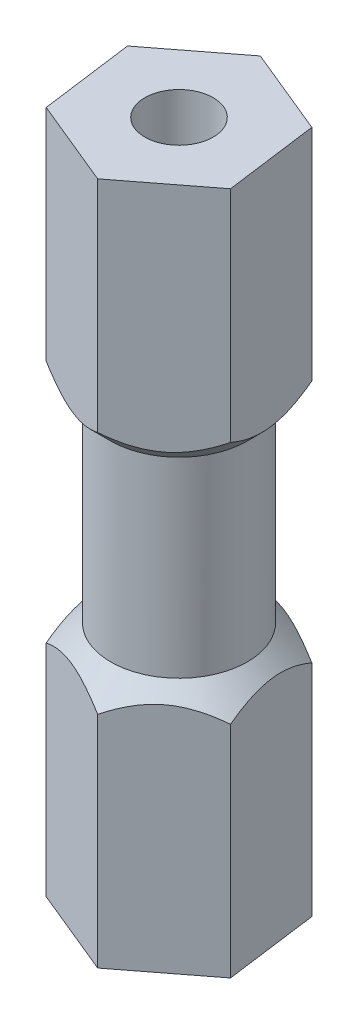
SolidWorks part; units mm, degrees
material "7050-T73510"
ref_plane "前视基准面" through (0, 0, 0) normal (0, 0, 1) x (1, 0, 0)
ref_plane "上视基准面" through (0, 0, 0) normal (0, 1, 0) x (1, 0, 0)
ref_plane "右视基准面" through (0, 0, 0) normal (1, 0, 0) x (0, 0, -1)
sketch "草图1" plane through (0, 0, 0) normal (0, 1, 0) x (1, 0, 0)
  circle A0 centre (0, 0) radius 2.5
  dimension "D1" = 5
extrude "凸台-拉伸1" add sketch "草图1" along normal blind 25
sketch "草图2" plane through (0, 25, 0) normal (0, 1, 0) x (1, 0, 0)
  line L1 (3.2029, -1.3196) -> (2.7443, 2.114)
  line L2 (2.7443, 2.114) -> (-0.4586, 3.4336)
  line L3 (-0.4586, 3.4336) -> (-3.2029, 1.3196)
  line L4 (-3.2029, 1.3196) -> (-2.7443, -2.114)
  line L5 (-2.7443, -2.114) -> (0.4586, -3.4336)
  line L6 (0.4586, -3.4336) -> (3.2029, -1.3196)
  circle A0 centre (0, 0) radius 3 construction
  dimension "D1" = 6
extrude "凸台-拉伸2" add sketch "草图2" against normal blind 8
sketch "草图3" plane through (0, 0, 0) normal (0, -1, 0) x (1, 0, 0)
  line L6 (3.2029, 1.3196) -> (0.4586, 3.4336)
  line L7 (0.4586, 3.4336) -> (-2.7443, 2.114)
  line L8 (-2.7443, 2.114) -> (-3.2029, -1.3196)
  line L9 (-3.2029, -1.3196) -> (-0.4586, -3.4336)
  line L10 (-0.4586, -3.4336) -> (2.7443, -2.114)
  line L11 (2.7443, -2.114) -> (3.2029, 1.3196)
  line L12 (3.2029, 1.3196) -> (0.4586, 3.4336)
  line L13 (0.4586, 3.4336) -> (-2.7443, 2.114)
  line L14 (-2.7443, 2.114) -> (-3.2029, -1.3196)
  line L15 (-3.2029, -1.3196) -> (-0.4586, -3.4336)
  line L16 (-0.4586, -3.4336) -> (2.7443, -2.114)
  line L17 (2.7443, -2.114) -> (3.2029, 1.3196)
  dimension "D1" = 0
extrude "凸台-拉伸3" add sketch "草图3" against normal blind 8
chamfer "倒角1" distance 1 angle 45 2 edges at (0, 8, -2.5) (0, 17, 2.5)
sketch "草图4" plane through (0, 0, 0) normal (0, 1, 0) x (-1, 0, 0)
  circle A0 centre (0, 0) radius 1.25
  dimension "D1" = 2.5
extrude "切除-拉伸1" cut sketch "草图4" along normal blind 8
cosmetic thread "装饰螺纹线2" parameters "D2"=3
sketch "草图5" plane through (0, 25, 0) normal (0, -1, 0) x (-1, 0, 0)
  circle A0 centre (0, 0) radius 1.25
  dimension "D1" = 2.5
extrude "切除-拉伸2" cut sketch "草图5" along normal blind 8
cosmetic thread "装饰螺纹线1" parameters "D2"=3
